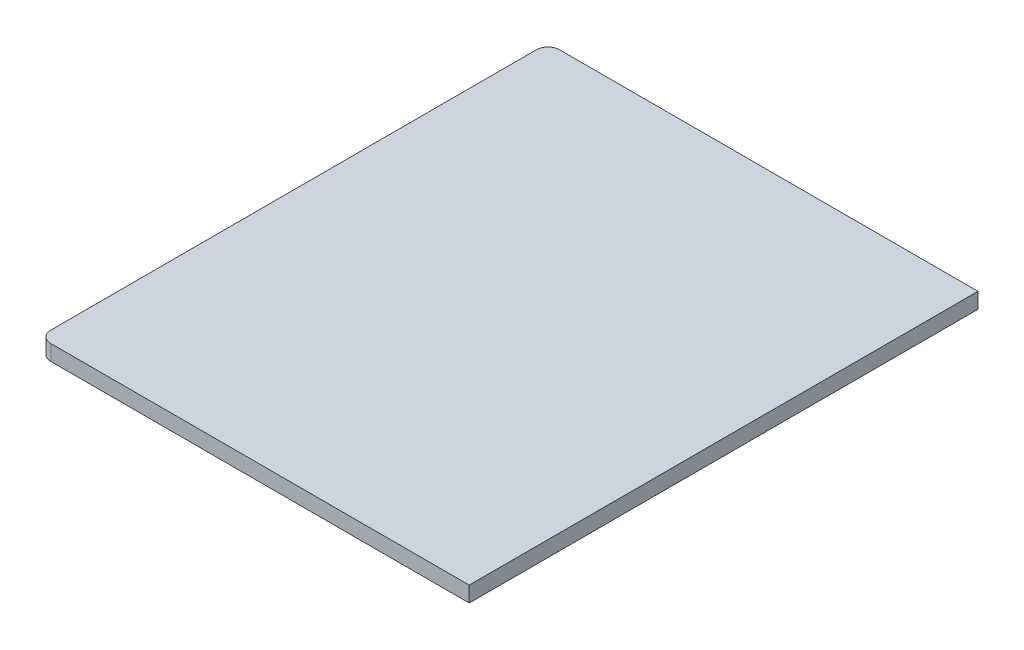
SolidWorks part; units mm, degrees
ref_plane "Front Plane" through (0, 0, 0) normal (0, 0, 1) x (1, 0, 0)
ref_plane "Top Plane" through (0, 0, 0) normal (0, 1, 0) x (1, 0, 0)
ref_plane "Right Plane" through (0, 0, 0) normal (1, 0, 0) x (0, 0, -1)
sketch "Sketch1" plane through (0, 0, 0) normal (0, 1, 0) x (1, 0, 0)
  line L0 (-124.873, 0) -> (36.3874, 0) construction
  line L1 (-63.4844, 44.0107) -> (-63.4844, 13.237) construction
  line L2 (-103, -60.9298) -> (-5, -60.9298) construction
  line L3 (-103, -60.9298) -> (-103, 60.9298) construction
  line L4 (-103, 60.9298) -> (-5, 60.9298) construction
  line L5 (-5, -60.9298) -> (-5, 60.9298) construction
  line L6 (-103, -60.9298) -> (-5, 60.9298) construction
  line L7 (-103, 60.9298) -> (-5, -60.9298) construction
  line L8 (-108, -65.9298) -> (-108, 65.9298) construction
  line L9 (-56.2, -7.05) -> (-42.1, -7.05) construction
  line L10 (-56.2, -7.05) -> (-56.2, 7.05) construction
  line L11 (-56.2, 7.05) -> (-42.1, 7.05) construction
  line L12 (-42.1, -7.05) -> (-42.1, 7.05) construction
  line L13 (-56.2, -7.05) -> (-42.1, 7.05) construction
  line L14 (-56.2, 7.05) -> (-42.1, -7.05) construction
  line L19 (-108, 65.9298) -> (0, 65.9298) construction
  line L20 (0, -65.9298) -> (0, 65.9298) construction
  line L21 (-108, -65.9298) -> (0, -65.9298) construction
  line L22 (-58.7, -9.55) -> (-58.7, 9.55) construction
  line L31 (-5.5, -9.55) -> (-24.6, -9.55) construction
  line L32 (-32.1, 26.444) -> (-22.1298, 36.4142) construction
  line L33 (-58.7, 9.55) -> (-39.6, 9.55) construction
  line L34 (-39.6, -9.55) -> (-39.6, 9.55) construction
  line L35 (-58.7, -9.55) -> (-39.6, -9.55) construction
  line L36 (-32.1, 79.121) -> (-32.1, -87.5553) construction
  line L41 (-32.1, 26.444) -> (-42.0702, 36.4142) construction
  line L42 (-42.0702, 36.4142) -> (-32.1, 46.3844) construction
  line L43 (-22.1298, 36.4142) -> (-32.1, 46.3844) construction
  line L44 (-32.1, 26.444) -> (-32.1, 46.3844) construction
  line L45 (-42.0702, 36.4142) -> (-22.1298, 36.4142) construction
  line L46 (-24.6, -9.55) -> (-24.6, 9.55) construction
  line L47 (-5.5, 9.55) -> (-24.6, 9.55) construction
  line L48 (-5.5, -9.55) -> (-5.5, 9.55) construction
  line L49 (-8, 7.05) -> (-22.1, 7.05) construction
  line L50 (-22.1, -7.05) -> (-22.1, 7.05) construction
  line L51 (-8, -7.05) -> (-22.1, -7.05) construction
  line L52 (-8, -7.05) -> (-8, 7.05) construction
  line L53 (-39.6, -3.1881) -> (-24.6, -3.1881) construction
  line L54 (-78.4844, 60.9298) -> (-78.4844, 36.4142) construction
  line L55 (-5.5, 4.2229) -> (9.5, 4.2229) construction
  line L56 (-39.15, -36.15) -> (-25.05, -36.15) construction
  line L57 (-39.15, -36.15) -> (-39.15, -22.05) construction
  line L58 (-39.15, -22.05) -> (-25.05, -22.05) construction
  line L59 (-25.05, -36.15) -> (-25.05, -22.05) construction
  line L60 (-39.15, -36.15) -> (-25.05, -22.05) construction
  line L61 (-39.15, -22.05) -> (-25.05, -36.15) construction
  line L62 (-51.2, -38.65) -> (-13, -38.65) construction
  line L63 (-51.2, -38.65) -> (-51.2, -19.55) construction
  line L64 (-51.2, -19.55) -> (-13, -19.55) construction
  line L65 (-13, -38.65) -> (-13, -19.55) construction
  line L66 (-51.2, -38.65) -> (-13, -19.55) construction
  line L67 (-51.2, -19.55) -> (-13, -38.65) construction
  line L68 (-78.4844, 36.4142) -> (-103, 36.4142) construction
  line L69 (-83.8844, 35.1642) -> (-73.0844, 35.1642) construction
  line L70 (-83.8844, 35.1642) -> (-83.8844, 37.6642) construction
  line L71 (-83.8844, 37.6642) -> (-73.0844, 37.6642) construction
  line L72 (-73.0844, 35.1642) -> (-73.0844, 37.6642) construction
  line L73 (-83.8844, 35.1642) -> (-73.0844, 37.6642) construction
  line L74 (-83.8844, 37.6642) -> (-73.0844, 35.1642) construction
  line L75 (-78.4844, 0) -> (-78.4844, 36.4142) construction
  line L76 (-78.4844, 36.4142) -> (-42.0702, 36.4142) construction
  line L77 (-32.1, 25.0298) -> (-43.4844, 36.4142) construction
  line L78 (-43.4844, 36.4142) -> (-32.1, 47.7986) construction
  line L79 (-20.7156, 36.4142) -> (-32.1, 47.7986) construction
  line L80 (-32.1, 25.0298) -> (-20.7156, 36.4142) construction
  line L81 (-105.9, -63.8298) -> (-105.9, 63.8298)
  line L82 (0, 65.9298) -> (2, 65.9298) construction
  line L83 (0, 65.9298) -> (0, -65.9298) construction
  line L84 (0, -65.9298) -> (2, -65.9298)
  line L85 (2, 65.9298) -> (2, -65.9298)
  line L86 (-105.9, 63.8298) -> (-2.1, 63.8298)
  line L87 (-2.1, -63.8298) -> (-2.1, 63.8298)
  line L88 (-105.9, -63.8298) -> (-2.1, -63.8298)
  line L89 (-2.1, -63.8298) -> (0, -63.8298)
  line L91 (0, 63.8298) -> (-2.1, 63.8298)
  line L92 (-2.1, 63.8298) -> (2, 63.8298)
  line L93 (2, 63.8298) -> (2, -63.8298)
  line L94 (2, -63.8298) -> (-2.1, -63.8298)
  circle A0 centre (-78.4844, 36.4142) radius 4.175 construction
  circle A1 centre (-78.4844, 36.4142) radius 15 construction
  circle A3 centre (-103, 60.9298) radius 2.9
  circle A4 centre (-103, -60.9298) radius 2.9
  circle A5 centre (-103, 60.9298) radius 2.1
  circle A6 centre (-5, 60.9298) radius 2.1
  circle A7 centre (-5, -60.9298) radius 2.1
  circle A8 centre (-103, -60.9298) radius 2.1
  point P3 (-54, 0)
  point P8 (-49.15, 0)
  point P21 (-32.1, 36.4142)
  point P26 (-32.1, -29.1)
  point P49 (-32.1, -29.1)
  point P69 (8.2421, 4.3254)
  point P83 (2, 4.2229)
  dimension "D11" = 8.35
  dimension "D14" = 30
  dimension "D16" = 4.2
  dimension "D4" = 14.1
  dimension "D3" = 2.5
  dimension "D5" = 19.1
  dimension "D6" = 38.2
  dimension "D7" = 10
  dimension "D8" = 15
  dimension "D12" = 2.5
  dimension "D13" = 10.8
  dimension "D15" = 20
  dimension "D17" = 2
  dimension "D10" = 110
  dimension "D1" = 5
  dimension "D2" = 2.5
  dimension "D9" = 1
  dimension "D18" = 2.1
extrude "Boss-Extrude1" add sketch "Sketch1" along normal blind 3.9 contours A4 L88 L87 L86 A3 L81 A7 A6 | A6 | A3 A5 | A5 | A4 A8 | A8 | A7 | L83 L91 L87 L89 | L94 L85 L92 L83 region at (-53.8924, 0, 0) region at (-103, 0, 58.1118) region at (-104.9926, 0, -62.9224) region at (-0.05, 0, 0) region at (-103, 0, -60.9298) region at (-5, 0, -60.9298) region at (-5, 0, 60.9298) region at (-103, 0, 60.9298)
extrude "Cut-Extrude1" cut sketch "Sketch1<6>" along normal blind 1.6 contours A6 | A8 | A7 | A5 region at (-5, 0, -60.9298) region at (-5, 0, 60.9298) region at (-103, 0, 60.9298)
sketch "Sketch1<6>" plane through (0, 0, 0) normal (0, 1, 0) x (1, 0, 0) same geometry as "Sketch1"
equation "\"Magnet Hole Dia\"= 4.2"
equation "\"Keyswitch Hole L\" = 14.1"
equation "\"Dial Hole Dia\" = 8.35"
equation "\"Dial Hole Rec L\"= 10.8"
equation "\"Dial Hole Rec W\"= 2.5"
equation "\"Wall Thickness\"= 5"
equation "\"Magnet Hole Depth\"= 1.6"
equation "\"Tape Hole L\"= 6"
equation "\"Tape Hole W\"= 2"
equation "\"D16@Sketch1\"=\"Magnet Hole Dia\""
equation "\"D1@Cut-Extrude1\"=\"Magnet Hole Depth\""
equation "\"D11@Sketch1\"=\"Dial Hole Dia\""
equation "\"D13@Sketch1\"=\"Dial Hole Rec L\""
equation "\"D12@Sketch1\"=\"Dial Hole Rec W\""
equation "\"D4@Sketch1\"=\"Keyswitch Hole L\""
equation "\"D1@Sketch1\"=\"Wall Thickness\""
